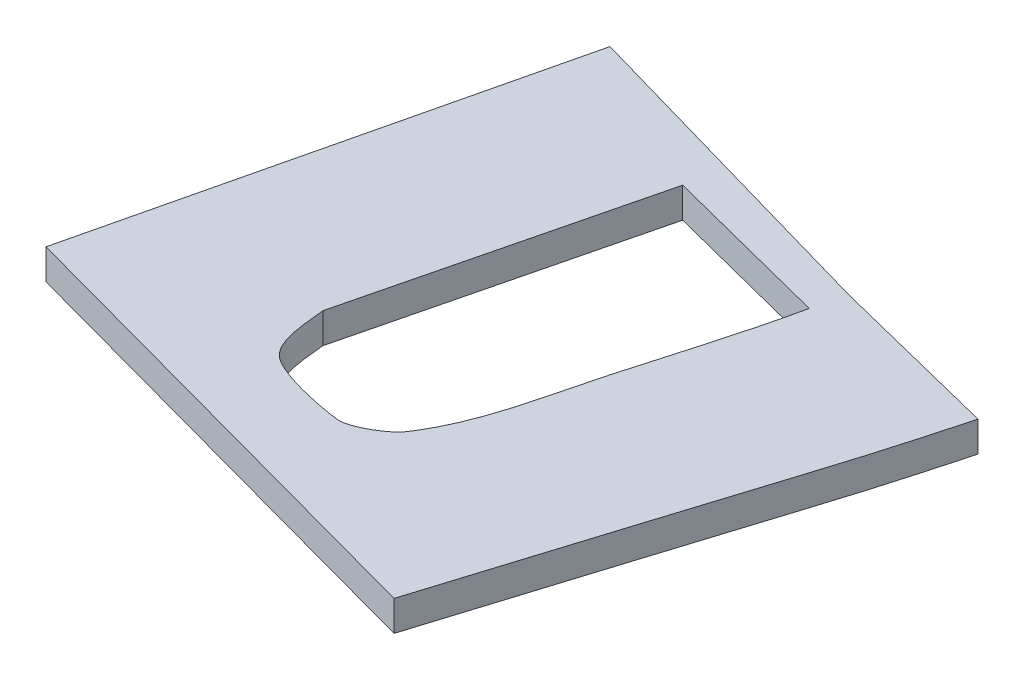
SolidWorks part; units mm, degrees
ref_plane "Front Plane" through (0, 0, 0) normal (0, 0, 1) x (1, 0, 0)
ref_plane "Top Plane" through (0, 0, 0) normal (0, 1, 0) x (1, 0, 0)
ref_plane "Right Plane" through (0, 0, 0) normal (1, 0, 0) x (0, 0, -1)
sketch "Sketch1" plane through (0, 0, 0) normal (0, 1, 0) x (1, 0, 0)
  line L0 (65.6854, -45.7865) -> (145.9282, -45.7865) construction
  line L2 (105.4165, 31.1383) -> (105.1558, -6.4062)
  line L3 (105.1558, -6.4062) -> (104.7647, -24.3962)
  line L4 (104.7647, -24.3962) -> (88.339, -24.1355)
  line L5 (88.339, -24.1355) -> (87.5568, 23.7076)
  line L6 (87.5568, 23.7076) -> (86.6443, 23.4469)
  line L7 (86.6443, 23.4469) -> (81.169, -31.0447)
  line L8 (81.169, -31.0447) -> (64.8737, -29.4804)
  line L9 (64.8737, -29.4804) -> (68.9149, 25.272)
  line L10 (68.9149, 25.272) -> (67.872, 25.1416)
  line L11 (67.872, 25.1416) -> (61.3539, -10.3171)
  line L12 (56.5305, -35.6074) -> (40.3655, -32.6091)
  line L13 (40.3655, -32.6091) -> (50.4034, 28.531)
  line L14 (50.4034, 28.531) -> (49.3605, 28.4007)
  line L15 (49.3605, 28.4007) -> (39.844, -6.1454)
  line L16 (32.8045, -31.0447) -> (17.0306, -26.7428)
  line L17 (17.0306, -26.7428) -> (21.0718, -9.7956)
  line L18 (21.0718, -9.7956) -> (27.7203, 14.5822)
  line L19 (27.7203, 14.5822) -> (34.3688, 40.6548)
  line L20 (39.844, 36.3528) -> (44.5371, 35.1795)
  line L21 (44.5371, 35.1795) -> (43.2335, 30.4865)
  line L22 (43.2335, 30.4865) -> (38.6708, 31.7901)
  line L23 (38.6708, 31.7901) -> (39.844, 36.3528)
  line L24 (57.7037, 32.3116) -> (62.5272, 31.399)
  line L25 (62.5272, 31.399) -> (61.6146, 26.706)
  line L26 (61.6146, 26.706) -> (56.9216, 27.4881)
  line L27 (56.9216, 27.4881) -> (57.7037, 32.3116)
  line L28 (75.8242, 29.7043) -> (80.6476, 29.1828)
  line L29 (80.6476, 29.1828) -> (80.2565, 24.4898)
  line L30 (80.2565, 24.4898) -> (75.4331, 24.8809)
  line L31 (75.4331, 24.8809) -> (75.8242, 29.7043)
  line L32 (37.3672, 28.9221) -> (42.9727, 27.3578)
  line L33 (31.7616, 7.4123) -> (37.3672, 28.9221)
  line L34 (94.2053, 28.6614) -> (99.0287, 28.531)
  line L35 (99.0287, 28.531) -> (98.8984, 23.838)
  line L36 (98.8984, 23.838) -> (94.2053, 23.9683)
  line L37 (94.2053, 23.9683) -> (94.2053, 28.6614)
  line L38 (55.8787, 24.4898) -> (61.4843, 23.5773)
  line L39 (61.4843, 23.5773) -> (61.6146, 23.0558)
  line L40 (74.6509, 21.7522) -> (80.5172, 21.2307)
  line L41 (93.6838, 20.7093) -> (99.5502, 20.5789)
  line L42 (99.4198, -9.0134) -> (93.6838, -8.8831)
  line L43 (31.6312, -14.8797) -> (26.156, -13.3154)
  line L44 (77.2581, -15.2708) -> (71.5222, -14.7494)
  line L45 (54.0536, -19.5728) -> (48.3176, -18.5299)
  line L46 (93.6838, -10.1867) -> (99.5502, -10.3171)
  line L47 (25.7649, -14.4887) -> (31.3705, -15.9226)
  line L48 (23.4183, -24.0051) -> (25.7649, -14.4887)
  line L49 (71.3918, -15.9226) -> (77.1278, -16.4441)
  line L50 (48.0569, -19.5728) -> (53.7929, -20.7461)
  spline S0 degree 3 poles (34.3688, 40.6548) (40.7566, 39.047) (47.0864, 37.1883) (53.5321, 35.8313) (59.4811, 34.5789) (65.4868, 33.5633) (71.5222, 32.833) (82.7525, 31.4742) (94.1059, 31.3316) (105.4165, 31.1383) knots 0 0 0 0 1 1 1 2 2 2 3 3 3 3
  spline S1 degree 3 poles (61.3539, -10.3171) (60.5564, -15.1018) (59.9234, -19.9204) (58.877, -24.657) (58.0717, -28.3021) (57.3126, -31.9573) (56.5305, -35.6074) knots 0 0 0 0 1 1 1 2 2 2 2
  spline S2 degree 3 poles (39.844, -6.1454) (38.6037, -10.974) (37.5703, -15.8635) (36.0635, -20.6157) (34.9627, -24.0875) (33.8908, -27.5684) (32.8045, -31.0447) knots 0 0 0 0 1 1 1 2 2 2 2
  spline S3 degree 3 poles (42.9727, 27.3578) (42.6098, 25.543) (42.0183, 23.7712) (41.5388, 22.0129) (40.5659, 18.4459) (39.615, 14.8641) (38.6708, 11.3232) (38.3128, 9.9807) (37.6374, 5.782) (36.3242, 5.0657) (36.0465, 4.9143) (35.7159, 4.8919) (35.4117, 4.805) knots 0 0 0 0 1 1 1 2 2 2 3 3 3 4 4 4 4
  spline S4 degree 3 poles (35.4117, 4.805) (35.3683, 4.8485) (35.3416, 4.9233) (35.2813, 4.9354) (34.8955, 5.0126) (34.4939, 4.9886) (34.1081, 5.0657) (32.6203, 5.3633) (32.0189, 5.8682) (31.7616, 7.4123) knots 0 0 0 0 1 1 1 2 2 2 3 3 3 3
  spline S5 degree 3 poles (61.6146, 23.0558) (61.5712, 23.0123) (61.4951, 22.9859) (61.4843, 22.9254) (61.1889, 21.28) (60.9974, 19.6171) (60.7021, 17.9717) (60.4799, 16.7336) (60.0077, 14.6452) (59.7895, 13.409) (59.5288, 11.9315) (59.2681, 10.4541) (59.0074, 8.9766) (58.5651, 6.4706) (58.3671, 3.9272) (57.5734, 1.546) (57.2884, 0.6909) (56.5034, 0.8671) (56.009, 0.3727) knots 0 0 0 0 1 1 1 2 2 2 3 3 3 4 4 4 5 5 5 6 6 6 6
  spline S6 degree 3 poles (56.009, 0.3727) (55.9656, 0.4161) (55.9396, 0.4949) (55.8787, 0.5031) (55.5536, 0.5464) (53.0297, 0.6407) (52.6196, 1.2852) (51.9043, 2.4092) (52.2987, 3.9943) (52.4892, 5.0657) (53.3606, 9.9671) (54.1038, 14.7799) (54.9661, 19.6664) (55.2268, 21.1438) (55.4876, 22.6213) (55.7483, 24.0987) (55.759, 24.1592) (55.8592, 24.1708) (55.8787, 24.2291) (55.9061, 24.3115) (55.8787, 24.4029) (55.8787, 24.4898) knots 0 0 0 0 1 1 1 2 2 2 3 3 3 4 4 4 5 5 5 6 6 6 7 7 7 7
  spline S7 degree 3 poles (80.5172, 21.2307) (80.0392, 15.6686) (79.6003, 10.1029) (79.0832, 4.5443) (79.0775, 4.4831) (78.963, 4.4746) (78.9529, 4.4139) (78.826, 3.6525) (78.8807, 1.9872) (77.91, 1.546) (77.5837, 1.3977) (77.2251, 1.3001) (76.8671, 1.2852) (74.9681, 1.2061) (73.2767, 1.3602) (73.2169, 3.6318) (73.1849, 4.8488) (73.2635, 6.0673) (73.3473, 7.2819) (73.3515, 7.3432) (73.4721, 7.3511) (73.4776, 7.4123) (73.9079, 12.1889) (74.2598, 16.9722) (74.6509, 21.7522) knots 0 0 0 0 1 1 1 2 2 2 3 3 3 4 4 4 5 5 5 6 6 6 7 7 7 8 8 8 8
  spline S8 degree 3 poles (99.5502, 20.5789) (99.5292, 18.1925) (100.7408, 9.6804) (99.1591, 4.9354) (99.0178, 4.5115) (98.3729, 4.0848) (97.9858, 4.0228) (97.3343, 3.9186) (94.7895, 3.5063) (94.2053, 4.6747) (94.0209, 5.0434) (93.8276, 5.4359) (93.8142, 5.8479) (93.6532, 10.7993) (93.7273, 15.7555) (93.6838, 20.7093) knots 0 0 0 0 1 1 1 2 2 2 3 3 3 4 4 4 5 5 5 5
  spline S9 degree 3 poles (93.6838, -8.8831) (93.7381, -4.9776) (93.2303, -1.8325) (94.0749, 1.546) (94.2734, 2.34) (95.3786, 2.8868) (96.1607, 2.8496) (96.8606, 2.8163) (97.5625, 2.7409) (98.2465, 2.5889) (98.4265, 2.5489) (98.5481, 2.3589) (98.6376, 2.1978) (98.8264, 1.858) (99.0648, 1.5319) (99.1591, 1.1549) (99.329, 0.4751) (99.4018, -0.2305) (99.4198, -0.9309) (99.4889, -3.6242) (99.4198, -6.3193) (99.4198, -9.0134) knots 0 0 0 0 1 1 1 2 2 2 3 3 3 4 4 4 5 5 5 6 6 6 7 7 7 7
  spline S10 degree 3 poles (26.156, -13.3154) (26.5473, -11.1629) (27.1698, -8.9703) (27.8507, -6.9276) (28.181, -5.9365) (28.5376, -4.1432) (29.2847, -3.1471) (30.1612, -1.9784) (33.0544, -2.5643) (33.717, -3.6686) (33.8584, -3.9042) (33.9663, -4.1761) (33.9777, -4.4507) (34.0665, -6.5814) (33.3414, -8.5642) (32.8045, -10.5778) (32.4111, -12.053) (32.0449, -13.4318) (31.6312, -14.8797) knots 0 0 0 0 1 1 1 2 2 2 3 3 3 4 4 4 5 5 5 6 6 6 6
  spline S11 degree 3 poles (71.5222, -14.7494) (71.7395, -12.0987) (71.9178, -9.4445) (72.174, -6.7973) (72.1799, -6.7361) (72.2915, -6.727) (72.3044, -6.6669) (72.4857, -5.8207) (72.4934, -4.085) (73.4776, -3.5382) (74.7635, -2.8238) (77.5508, -3.0117) (77.7796, -4.8418) (78.1927, -8.1469) (77.532, -12.0533) (77.2581, -15.2708) knots 0 0 0 0 1 1 1 2 2 2 3 3 3 4 4 4 5 5 5 5
  spline S12 degree 3 poles (48.3176, -18.5299) (48.4682, -17.6074) (49.3932, -9.6418) (50.7945, -7.8402) (51.7213, -6.6485) (54.6235, -7.2853) (55.2268, -8.492) (55.8006, -9.6395) (55.3934, -11.4371) (55.2268, -12.4029) (55.0096, -13.663) (54.8079, -14.926) (54.575, -16.1834) (54.3669, -17.3074) (54.2274, -18.443) (54.0536, -19.5728) knots 0 0 0 0 1 1 1 2 2 2 3 3 3 4 4 4 5 5 5 5
  spline S13 degree 3 poles (99.5502, -10.3171) (99.5067, -13.3154) (99.5054, -16.3146) (99.4198, -19.3121) (99.418, -19.3735) (99.3015, -19.3822) (99.2894, -19.4424) (99.1051, -20.3644) (99.0318, -21.7625) (97.7251, -21.9193) (97.6585, -21.9273) (95.19, -22.2702) (94.5964, -21.5282) (94.042, -20.8353) (93.862, -19.7496) (93.8142, -18.921) (93.7141, -17.1852) (93.7098, -15.445) (93.6838, -13.7065) (93.6663, -12.5333) (93.6838, -11.36) (93.6838, -10.1867) knots 0 0 0 0 1 1 1 2 2 2 3 3 3 4 4 4 5 5 5 6 6 6 7 7 7 7
  spline S14 degree 3 poles (31.3705, -15.9226) (30.9772, -17.7579) (30.4209, -19.4915) (29.9365, -21.2675) (29.4951, -22.8858) (29.203, -24.6491) (28.2418, -26.0909) (28.0279, -26.4117) (27.2093, -26.8922) (26.8078, -26.8731) (26.4958, -26.8583) (24.4443, -26.5211) (23.9398, -25.9606) (23.5046, -25.477) (23.4904, -24.5814) (23.4183, -24.0051) knots 0 0 0 0 1 1 1 2 2 2 3 3 3 4 4 4 5 5 5 5
  spline S15 degree 3 poles (77.1278, -16.4441) (77.1137, -16.6412) (76.8294, -26.002) (75.5634, -27.3946) (75.0354, -27.9754) (74.4265, -27.9481) (73.7383, -28.0464) knots 0 0 0 0 1 1 1 2 2 2 2
  spline S16 degree 3 poles (73.7383, -28.0464) (73.1325, -27.4405) (72.0165, -28.1085) (71.3918, -27.3946) (70.9276, -26.864) (70.7525, -25.5861) (70.74, -25.048) (70.7087, -23.7006) (70.7863, -22.352) (70.8704, -21.0068) (70.8742, -20.9455) (70.9945, -20.9376) (71.0007, -20.8764) (71.1697, -19.2287) (71.2615, -17.5739) (71.3918, -15.9226) knots 0 0 0 0 1 1 1 2 2 2 3 3 3 4 4 4 5 5 5 5
  spline S17 degree 3 poles (53.7929, -20.7461) (53.7097, -21.2553) (52.6819, -29.4762) (51.4463, -31.1751) (50.4846, -32.4974) (47.0812, -32.066) (46.7533, -30.2625) (46.3263, -27.9143) (47.1317, -25.3533) (47.5354, -23.0926) (47.7439, -21.925) (47.8831, -20.7461) (48.0569, -19.5728) knots 0 0 0 0 1 1 1 2 2 2 3 3 3 4 4 4 4
  dimension "D1" = 16.35
extrude "Boss-Extrude1" add sketch "Sketch1" along normal blind 1
sketch "Sketch2" plane through (0, 1, 0) normal (0, 1, 0) x (1, 0, 0)
  line L0 (34.3688, 40.6548) -> (34.1217, 39.6858)
  line L1 (34.3688, 40.6548) -> (27.7203, 14.5822) construction
  line L6 (105.1558, -6.4062) -> (105.4165, 31.1383) construction
  line L7 (105.4095, 30.1383) -> (105.4165, 31.1383)
  arc A0 (34.3688, 40.6548) -> (105.4165, 31.1383) centre (102.0623, 276.0676) ccw
  arc A1 (34.1217, 39.6858) -> (105.4095, 30.1383) centre (102.1959, 277.0586) ccw
  dimension "D1" = 1
  dimension "D2" = 1
  dimension "D3" = 1
extrude "Boss-Extrude2" add sketch "Sketch2" along normal blind 2.42 and the other way blind 1
fillet "Fillet1" radius 0.5 2 edges at (69.5427, 3.42, -33.2836) (69.4162, 3.42, -32.3027)
sketch "Sketch3" plane through (0, 1, 0) normal (0, 1, 0) x (1, 0, 0)
  line L20 (37.3672, 28.9221) -> (42.9727, 27.3578)
  line L39 (42.9727, 27.3578) -> (48.6429, 25.7958)
  line L40 (39.844, -6.1454) -> (49.3605, 28.4007) construction
  line L41 (37.3672, 28.9221) -> (31.7427, 30.3564)
  line L42 (34.1217, 39.6858) -> (27.7203, 14.5822) construction
  line L43 (31.7427, 30.3564) -> (31.9898, 31.3253)
  line L45 (48.9085, 26.7599) -> (48.6429, 25.7958)
  line L46 (31.9898, 31.3253) -> (48.9085, 26.7599)
  line L47 (55.8787, 24.4898) -> (61.4843, 23.5773)
  line L48 (61.4843, 23.5773) -> (67.4072, 22.613)
  line L49 (61.3539, -10.3171) -> (67.872, 25.1416) construction
  line L50 (55.8787, 24.4898) -> (49.9011, 25.4712)
  line L51 (50.4034, 28.531) -> (40.3655, -32.6091) construction
  line L52 (49.9011, 25.4712) -> (50.0631, 26.458)
  line L53 (67.4072, 22.613) -> (67.588, 23.5966)
  line L54 (50.0631, 26.458) -> (67.588, 23.5966)
  line L55 (74.6509, 21.7522) -> (80.5172, 21.2307)
  line L56 (80.5172, 21.2307) -> (74.6509, 21.7522) construction
  line L57 (80.5172, 21.2307) -> (86.3626, 20.6434)
  line L58 (81.169, -31.0447) -> (86.6443, 23.4469) construction
  line L59 (74.6509, 21.7522) -> (68.6876, 22.1923)
  line L60 (68.9149, 25.272) -> (64.8737, -29.4804) construction
  line L61 (68.6876, 22.1923) -> (68.7612, 23.1896)
  line L62 (86.3626, 20.6434) -> (86.4625, 21.6384)
  line L63 (68.7612, 23.1896) -> (86.4625, 21.6384)
  line L64 (93.6838, 20.7093) -> (99.5502, 20.5789)
  line L65 (99.5502, 20.5789) -> (105.3432, 20.5789)
  line L66 (105.1558, -6.4062) -> (105.4095, 30.1383) construction
  line L67 (93.6838, 20.7093) -> (87.6036, 20.8444)
  line L68 (87.5568, 23.7076) -> (88.339, -24.1355) construction
  line L69 (87.6036, 20.8444) -> (87.5873, 21.8443)
  line L70 (105.3432, 20.5789) -> (105.3501, 21.5789)
  line L71 (87.5873, 21.8443) -> (105.3501, 21.5789)
  spline S0 degree 3 poles (74.6509, 21.7522) (74.2598, 16.9722) (73.9079, 12.1889) (73.4776, 7.4123) (73.4721, 7.3511) (73.3515, 7.3432) (73.3473, 7.2819) (73.2635, 6.0673) (73.1849, 4.8488) (73.2169, 3.6318) (73.2767, 1.3602) (74.9681, 1.2061) (76.8671, 1.2852) (77.2251, 1.3001) (77.5837, 1.3977) (77.91, 1.546) (78.8807, 1.9872) (78.826, 3.6525) (78.9529, 4.4139) (78.963, 4.4746) (79.0775, 4.4831) (79.0832, 4.5443) (79.6003, 10.1029) (80.0392, 15.6686) (80.5172, 21.2307) knots 0 0 0 0 1 1 1 2 2 2 3 3 3 4 4 4 5 5 5 6 6 6 7 7 7 8 8 8 8 construction
  dimension "D1" = 1
  dimension "D2" = 1
  dimension "D3" = 1
  dimension "D4" = 1
  dimension "D5" = 1
  dimension "D6" = 1
  dimension "D7" = 1
  dimension "D8" = 1
extrude "Boss-Extrude3" add sketch "Sketch3" along normal blind 2.42
fillet "Fillet2" radius 0.45 14 edges at (52.8899, 3.42, -24.9805) (61.6429, 3.42, -23.5514) (71.6693, 3.42, -21.9722) (83.4399, 3.42, -20.9371) (77.584, 3.42, -21.4914) (102.4467, 3.42, -20.5789) (93.5769, 3.42, -20.7117) (96.4687, 3.42, -21.7116) (77.6119, 3.42, -22.414) (58.8255, 3.42, -25.0273) (40.4492, 3.42, -29.0426) (34.5549, 3.42, -29.6392) (45.8078, 3.42, -26.5768) (40.1699, 3.42, -28.1399)
sketch "Sketch4" plane through (0, 1, 0) normal (0, 1, 0) x (1, 0, 0)
  line L0 (30.8433, 26.8292) -> (34.884, 25.7988)
  line L3 (47.4107, 21.3224) -> (43.3904, 22.4299)
  line L4 (39.844, -6.1454) -> (48.6429, 25.7958) construction
  line L5 (31.7427, 30.3564) -> (27.7203, 14.5822) construction
  line L6 (34.884, 25.7988) -> (34.6369, 24.8299)
  line L7 (34.6369, 24.8299) -> (30.5962, 25.8602)
  line L8 (30.5962, 25.8602) -> (30.8433, 26.8292)
  line L9 (43.3904, 22.4299) -> (43.656, 23.394)
  line L10 (43.656, 23.394) -> (47.6762, 22.2865)
  line L11 (47.6762, 22.2865) -> (47.4107, 21.3224)
  line L12 (31.7427, 30.3564) -> (37.3672, 28.9221) construction
  line L13 (48.6429, 25.7958) -> (42.9727, 27.3578) construction
  line L14 (49.3113, 21.8793) -> (53.3473, 21.2167)
  line L15 (49.9011, 25.4712) -> (40.3655, -32.6091) construction
  line L16 (53.3473, 21.2167) -> (53.1853, 20.2299)
  line L17 (53.1853, 20.2299) -> (49.1493, 20.8925)
  line L18 (49.3113, 21.8793) -> (49.1493, 20.8925)
  line L19 (49.9011, 25.4712) -> (55.8787, 24.4898) construction
  line L27 (66.7491, 19.033) -> (62.7265, 19.7725)
  line L28 (61.3539, -10.3171) -> (67.4072, 22.613) construction
  line L29 (62.7265, 19.7725) -> (62.5457, 18.789)
  line L30 (62.5457, 18.789) -> (66.5683, 18.0495)
  line L32 (66.5683, 18.0495) -> (66.7491, 19.033)
  line L33 (68.3461, 17.5649) -> (72.425, 17.2638)
  line L34 (68.6876, 22.1923) -> (64.8737, -29.4804) construction
  line L35 (72.425, 17.2638) -> (72.4986, 18.2611)
  line L36 (72.4986, 18.2611) -> (68.4197, 18.5622)
  line L37 (68.4197, 18.5622) -> (68.3461, 17.5649)
  line L38 (68.6876, 22.1923) -> (74.6509, 21.7522) construction
  line L39 (85.8987, 16.0266) -> (81.8292, 16.4355)
  line L40 (81.169, -31.0447) -> (86.3626, 20.6434) construction
  line L41 (81.8292, 16.4355) -> (81.9291, 17.4305)
  line L42 (81.9291, 17.4305) -> (85.9987, 17.0216)
  line L43 (85.9987, 17.0216) -> (85.8987, 16.0266)
  line L44 (80.5172, 21.2307) -> (86.3626, 20.6434) construction
  line L45 (87.681, 16.111) -> (91.771, 16.1779)
  line L46 (87.6036, 20.8444) -> (88.339, -24.1355) construction
  line L47 (91.771, 16.1779) -> (91.771, 17.1109)
  line L48 (91.771, 17.1109) -> (87.6646, 17.1109)
  line L49 (87.6646, 17.1109) -> (87.681, 16.111)
  line L52 (87.6036, 20.8444) -> (93.6838, 20.7093) construction
  line L53 (105.3179, 16.9389) -> (101.2211, 16.9674)
  line L54 (105.1558, -6.4062) -> (105.3432, 20.5789) construction
  line L55 (101.2211, 16.9674) -> (101.2211, 15.9674)
  line L56 (101.2211, 15.9674) -> (105.3111, 15.9674)
  line L57 (105.3111, 15.9674) -> (105.3179, 16.9389)
  point P16 (43.5232, 22.9119)
  dimension "D1" = 3.64
  dimension "D2" = 1
  dimension "D3" = 4.17
  dimension "D4" = 3.64
  dimension "D5" = 1
  dimension "D6" = 4.17
  dimension "D7" = 3.64
  dimension "D8" = 1
  dimension "D9" = 4.09
  dimension "D10" = 3.64
  dimension "D11" = 1
  dimension "D12" = 4.09
  dimension "D13" = 3.64
  dimension "D14" = 1
  dimension "D15" = 4.09
  dimension "D16" = 3.64
  dimension "D17" = 1
  dimension "D18" = 4.09
  dimension "D19" = 1
  dimension "D20" = 4.09
  dimension "D21" = 3.64
  dimension "D22" = 1
  dimension "D23" = 4.09
  dimension "D24" = 3.64
extrude "Boss-Extrude4" add sketch "Sketch4" along normal blind 2.42
fillet "Fillet3" radius 0.45 16 edges at (103.2661, 3.42, -15.9674) (103.2695, 3.42, -16.9531) (89.726, 3.42, -16.1444) (89.7178, 3.42, -17.1109) (83.9639, 3.42, -17.2261) (83.8639, 3.42, -16.2311) (70.3855, 3.42, -17.4144) (70.4591, 3.42, -18.4117) (64.7378, 3.42, -19.4028) (64.557, 3.42, -18.4192) (51.1673, 3.42, -20.5612) (51.3293, 3.42, -21.548) (45.6661, 3.42, -22.8402) (45.4005, 3.42, -21.8762) (32.8636, 3.42, -26.314) (32.6165, 3.42, -25.345)
sketch "Sketch5" plane through (0, 1, 0) normal (0, 1, 0) x (1, 0, 0)
  line L1 (21.0718, -9.7956) -> (17.0306, -26.7428) construction
  line L9 (26.156, -13.3154) -> (20.6103, -11.7309)
  line L10 (20.6103, -11.7309) -> (30.3161, 24.7619)
  line L11 (30.5962, 25.8602) -> (27.7203, 14.5822) construction
  line L12 (30.3161, 24.7619) -> (47.1265, 20.2909)
  line L13 (39.844, -6.1454) -> (47.4107, 21.3224) construction
  line L14 (47.1265, 20.2909) -> (37.3121, -16.3)
  line L15 (37.3121, -16.3) -> (31.6312, -14.8797)
  line L16 (31.6312, -14.8797) -> (26.156, -13.3154)
  spline S1 degree 3 poles (32.8045, -31.0447) (33.8908, -27.5684) (34.9627, -24.0875) (36.0635, -20.6157) (37.5703, -15.8635) (38.6037, -10.974) (39.844, -6.1454) knots 0 0 0 0 1 1 1 2 2 2 2 construction
extrude "Cut-Extrude1" cut sketch "Sketch5" against normal blind 10
sketch "Sketch6" plane through (0, 1, 0) normal (0, 1, 0) x (1, 0, 0)
  line L0 (20.6103, -11.7309) -> (21.3997, -2.7749)
  line L1 (21.3997, -2.7749) -> (23.4259, -1.4474)
  line L2 (23.4259, -1.4474) -> (25.0787, -6.8746)
  line L3 (25.0787, -6.8746) -> (20.6103, -11.7309)
extrude "Cut-Extrude2" cut sketch "Sketch6" against normal blind 10
sketch "Sketch7" plane through (0, 0, 0) normal (0, -1, 0) x (1, 0, 0)
  line L0 (25.0263, -26.1108) -> (40.7546, 17.4318)
  line L1 (40.7546, 17.4318) -> (37.6045, 36.3088)
  line L2 (37.6045, 36.3088) -> (114.7193, 39.476)
  line L3 (114.7193, 39.476) -> (107.1717, -33.8006)
  line L4 (107.1717, -33.8006) -> (27.9402, -43.3885)
  line L5 (27.9402, -43.3885) -> (25.0263, -26.1108)
extrude "Cut-Extrude3" cut sketch "Sketch7" against normal blind 10
